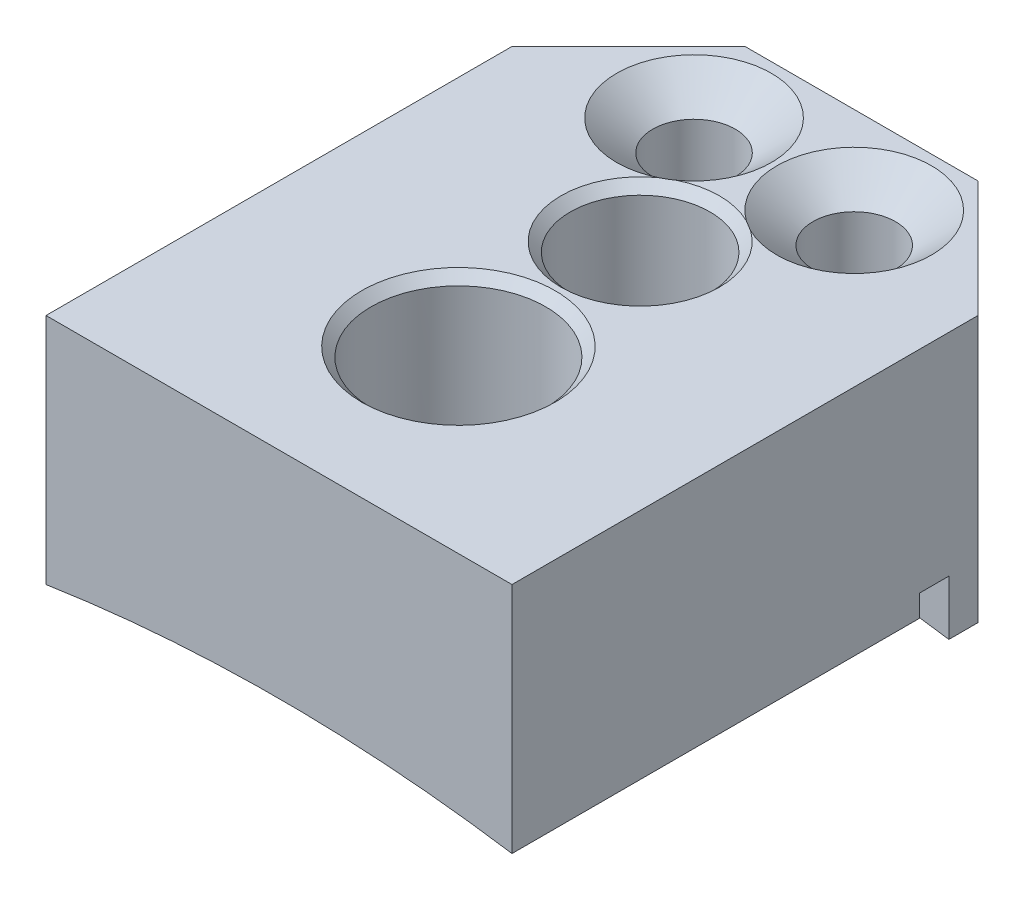
SolidWorks part; units mm, degrees
ref_plane "Front Plane" through (0, 0, 0) normal (0, 0, 1) x (1, 0, 0)
ref_plane "Top Plane" through (0, 0, 0) normal (0, 1, 0) x (1, 0, 0)
ref_plane "Right Plane" through (0, 0, 0) normal (1, 0, 0) x (0, 0, -1)
sketch "Sketch1" plane through (0, 0, 0) normal (0, 1, 0) x (1, 0, 0)
  line L0 (-28.5118, 12.8453) -> (-22.1618, 19.1953)
  line L1 (-22.1618, 19.1953) -> (-9.4618, 19.1953)
  line L2 (-28.5118, 12.8453) -> (-28.5118, -12.5547)
  line L3 (-28.5118, -12.5547) -> (-3.1118, -12.5547)
  line L4 (-3.1118, 12.8453) -> (-3.1118, -12.5547)
  line L5 (-9.4618, 19.1953) -> (-3.1118, 12.8453)
  line L6 (-15.8118, -12.5547) -> (-15.8118, 19.1953) construction
  line L8 (-3.1118, 12.8453) -> (-3.1118, 19.1953) construction
  line L9 (-3.1118, 19.1953) -> (-9.4618, 19.1953) construction
  dimension "D1" = 12.7
  dimension "D2" = 31.75
  dimension "D3" = 25.4
extrude "Boss-Extrude1" add sketch "Sketch1" along normal blind 12.7
sketch "Sketch2" plane through (0, 0, 12.5547) normal (0, 0, 1) x (1, 0, 0)
  circle A0 centre (-15.8118, -82.8523) radius 83.82
  dimension "D1" = 167.64
extrude "Cut-Extrude1" cut sketch "Sketch2" against normal through all both and the other way through all
sketch "Sketch5" plane through (0, 0, -19.1953) normal (0, 0, -1) x (-1, 0, 0)
  line L0 (3.1118, 12.7) -> (3.1118, 0) construction
  line L1 (3.1118, 12.7) -> (3.1118, 0)
  line L4 (28.5118, 12.7) -> (28.5118, 0) construction
  line L5 (28.5118, 12.7) -> (28.5118, 0)
  line L6 (28.5118, -1.7992) -> (28.5118, 0)
  line L7 (3.1118, -1.7992) -> (3.1118, 0)
  line L8 (3.1118, 12.7) -> (28.5118, 12.7)
  arc A0 (3.1118, -1.7992) -> (28.5118, -1.7992) centre (15.8118, -82.8523) cw
  arc A1 (28.5118, 0) -> (3.1118, 0) centre (15.8118, -82.8523) ccw construction
  arc A2 (28.5118, 0) -> (3.1118, 0) centre (15.8118, -82.8523) ccw construction
  dimension "D1" = 82.042
extrude "Boss-Extrude2" add sketch "Sketch5" against normal blind 7.9375
chamfer "Chamfer1" distance 6.35 angle 45 2 edges at (-28.5118, 5.4504, -19.1953) (-3.1118, 5.4504, -19.1953)
hole_wizard "CSK for #8 Flat Head Machine Screw (100)1" positions "Sketch3" profile "Sketch4" countersink size "#8" standard "ANSI Inch" end condition through all
sketch "Sketch3" plane through (0, 12.7, 0) normal (0, 1, 0) x (1, 0, 0)
  line L0 (-15.8118, 19.1953) -> (-15.8118, 3.4006) construction
  line L1 (-9.4618, 19.1953) -> (-22.1618, 19.1953) construction
  point P0 (-20.1775, 14.4328)
  point P12 (-11.4462, 14.4328)
  dimension "D1" = 4.7625
  dimension "D2" = 4.3656
sketch "Sketch4" plane through (-20.1775, 12.7, -14.4328) normal (1, 0, 0) x (0, 0, 1)
  line L0 (0, 0) -> (0, 14.4992)
  line L1 (0, 14.4992) -> (2.2479, 14.4992)
  line L2 (2.2479, 14.4992) -> (2.2479, 1.6518)
  line L3 (2.2479, 1.6518) -> (4.2164, 0)
  line L5 (4.2164, 0) -> (0, 0)
  line L6 (-2.2479, 1.6518) -> (-4.2164, 0) construction
  line L11 (0, -6.35) -> (0, 107.95) construction
  dimension "Thru Hole Dia." = 4.4958
  dimension "Thru Hole Depth" = 14.4992
  dimension "Near C'Sink Dia." = 8.4328
  dimension "Near C'Sink Angle" = 100
sketch "Sketch6" plane through (0, 12.7, 0) normal (0, 1, 0) x (1, 0, 0)
  line L0 (-15.8118, 19.1953) -> (-15.8118, -12.5547) construction
  line L1 (-9.4618, 19.1953) -> (-22.1618, 19.1953) construction
  line L2 (-28.5118, -12.5547) -> (-3.1118, -12.5547) construction
  circle A0 centre (-15.8118, 7.1303) radius 1.6319
  circle A1 centre (-15.8118, -2.7758) radius 1.5239
  spline S0 degree 3 poles (-15.9109, -10.6497) (-15.6088, -10.6497) (-15.4088, -10.6093) (-15.0421, -10.4569) (-14.8723, -10.3433) (-14.6614, -10.1321) (-14.5971, -10.0536) (-14.4867, -9.888) (-14.44, -9.8004) (-14.3254, -9.523) (-14.286, -9.3252) (-14.2863, -9.0237) (-14.2962, -8.9248) (-14.3351, -8.7299) (-14.3646, -8.633) (-14.4412, -8.4488) (-14.488, -8.3613) (-14.5989, -8.1955) (-14.6633, -8.1172) (-14.8743, -7.9067) (-15.0444, -7.7932) (-15.4113, -7.6415) (-15.6118, -7.6017) (-15.9102, -7.6018) (-16.0112, -7.6118) (-16.2064, -7.6508) (-16.3014, -7.6796) (-16.5784, -7.7944) (-16.7462, -7.9063) (-16.9595, -8.1198) (-17.0224, -8.1968) (-17.1327, -8.362) (-17.1804, -8.4512) (-17.2567, -8.6357) (-17.2855, -8.7307) (-17.3244, -8.9262) (-17.3342, -9.0271) (-17.3341, -9.3253) (-17.2941, -9.5259) (-17.142, -9.8926) (-17.0285, -10.0627) (-16.8176, -10.2736) (-16.7392, -10.3379) (-16.5735, -10.4485) (-16.486, -10.4953) (-16.3014, -10.5718) (-16.2047, -10.6011) (-16.0099, -10.6398) (-15.9109, -10.6497) (-15.6088, -10.6497) (-15.4088, -10.6093) knots -0.03125 -0.03125 0 0 0.0625 0.0625 0.125 0.125 0.15625 0.15625 0.1875 0.1875 0.25 0.25 0.28125 0.28125 0.3125 0.3125 0.34375 0.34375 0.375 0.375 0.4375 0.4375 0.5 0.5 0.53125 0.53125 0.5625 0.5625 0.625 0.625 0.65625 0.65625 0.6875 0.6875 0.71875 0.71875 0.75 0.75 0.8125 0.8125 0.875 0.875 0.90625 0.90625 0.9375 0.9375 0.96875 0.96875 1 1 1.0625 1.0625 1.125 only from (-15.8118, -4.2997) to (-15.8118, -4.2997) construction
  spline S2 degree 3 poles (-17.442, 0.8881) (-17.442, 0.5646) (-17.3987, 0.3504) (-17.2355, -0.0422) (-17.1139, -0.2241) (-16.8877, -0.4499) (-16.8036, -0.5187) (-16.6263, -0.6369) (-16.5325, -0.687) (-16.2355, -0.8097) (-16.0236, -0.8519) (-15.7008, -0.8516) (-15.5949, -0.8409) (-15.3862, -0.7993) (-15.2825, -0.7677) (-15.0851, -0.6857) (-14.9915, -0.6355) (-14.814, -0.5168) (-14.7301, -0.4479) (-14.5047, -0.222) (-14.3832, -0.0397) (-14.2207, 0.3532) (-14.178, 0.5678) (-14.1782, 0.8874) (-14.1889, 0.9955) (-14.2306, 1.2046) (-14.2615, 1.3063) (-14.3435, 1.5041) (-14.3946, 1.5994) (-14.5128, 1.7761) (-14.5805, 1.8587) (-14.7329, 2.0109) (-14.8153, 2.0784) (-14.9922, 2.1965) (-15.0878, 2.2476) (-15.2854, 2.3293) (-15.3871, 2.3601) (-15.5964, 2.4017) (-15.7045, 2.4123) (-16.0238, 2.4121) (-16.2385, 2.3692) (-16.6313, 2.2065) (-16.8134, 2.0849) (-17.0392, 1.8591) (-17.1081, 1.7751) (-17.2266, 1.5977) (-17.2767, 1.5039) (-17.3586, 1.3063) (-17.39, 1.2027) (-17.4314, 0.9941) (-17.442, 0.8881) (-17.442, 0.5646) (-17.3987, 0.3504) knots -0.03125 -0.03125 0 0 0.0625 0.0625 0.125 0.125 0.15625 0.15625 0.1875 0.1875 0.25 0.25 0.28125 0.28125 0.3125 0.3125 0.34375 0.34375 0.375 0.375 0.4375 0.4375 0.5 0.5 0.53125 0.53125 0.5625 0.5625 0.59375 0.59375 0.625 0.625 0.65625 0.65625 0.6875 0.6875 0.71875 0.71875 0.75 0.75 0.8125 0.8125 0.875 0.875 0.90625 0.90625 0.9375 0.9375 0.96875 0.96875 1 1 1.0625 1.0625 1.125 only from (-16.218, 5.5497) to (-16.218, 5.5497) construction
  point P6 (0, 0)
  point P7 (0, 0)
  point P8 (0, 0)
  point P10 (0, 0)
  point P11 (0, 0)
  dimension "D1" = 3.2639
  dimension "D2" = 3.0479
  dimension "D3" = 12.065
  dimension "D4" = 21.9711
extrude "Cut-Extrude2" cut sketch "Sketch6" against normal through all
sketch "Sketch7" plane through (-28.5118, 0, 0) normal (-1, 0, 0) x (0, 0, 1)
  line L1 (-11.2578, 0) -> (-9.6703, 0)
  line L2 (-11.2578, 0) -> (-11.2578, 1.1906)
  line L3 (-11.2578, 1.1906) -> (-9.6703, 1.1906)
  line L4 (-9.6703, 0) -> (-9.6703, 1.1906)
  dimension "D1" = 1.5875
  dimension "D2" = 1.1906
extrude "Cut-Extrude3" cut sketch "Sketch7" against normal through all
sketch "Sketch8" plane through (0, 12.7, 0) normal (0, 1, 0) x (1, 0, 0)
  line L0 (-15.8118, 3.3203) -> (-15.8118, 1.9867) construction
  circle A0 centre (-15.8118, -2.7758) radius 4.7625
  circle A1 centre (-15.8118, 7.1303) radius 3.81
  dimension "D2" = 9.525
  dimension "D1" = 7.62
extrude "Cut-Extrude4" cut sketch "Sketch8" against normal through all
chamfer "Chamfer2" distance 0.508 angle 45 2 edges at (-15.8118, 12.7, -3.3203) (-15.8118, 12.7, 7.5383)
